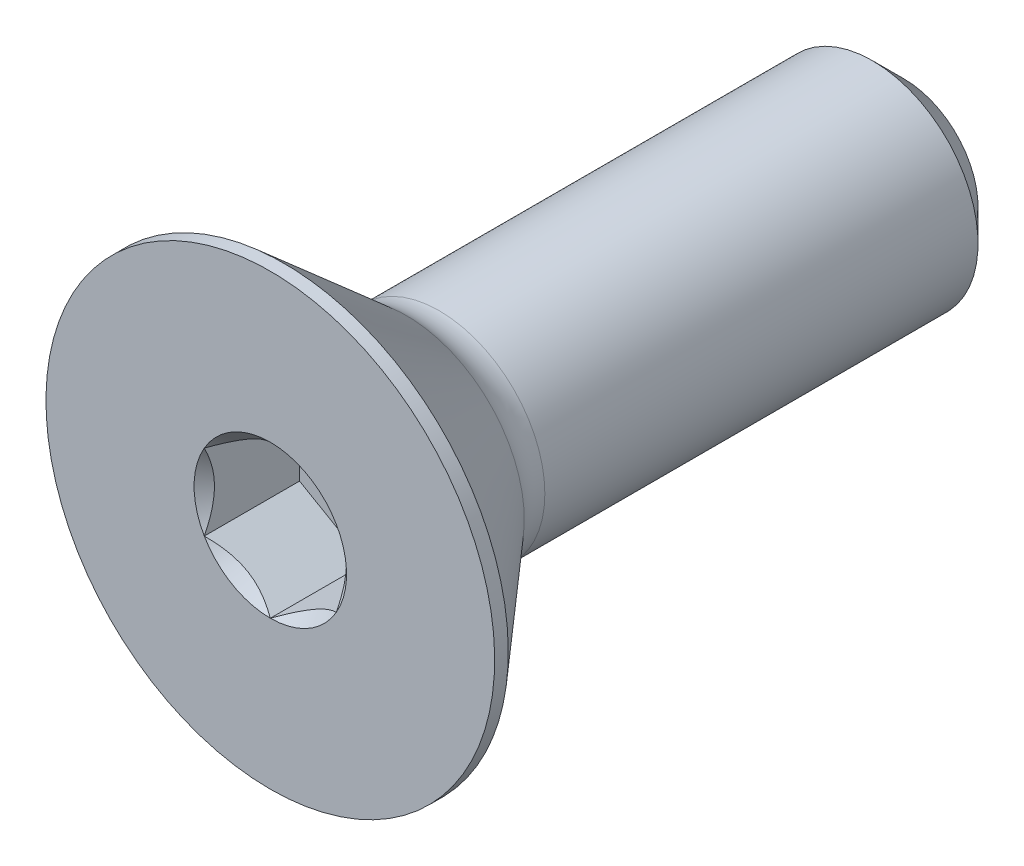
SolidWorks part; units mm, degrees
ref_plane "Front" through (0, 0, 0) normal (0, 0, 1) x (1, 0, 0)
ref_plane "Top" through (0, 0, 0) normal (0, 1, 0) x (1, 0, 0)
ref_plane "Right" through (0, 0, 0) normal (1, 0, 0) x (0, 0, -1)
sketch "Sketch1" plane through (0, 0, 0) normal (1, 0, 0) x (0, 0, -1)
  line L0 (0, 6.7437) -> (0.4089, 6.7437) construction
  line L1 (0.4089, 6.7437) -> (4.0894, 3.5443) construction
  line L2 (0, 3.175) -> (19.05, 3.175)
  line L3 (19.05, 3.175) -> (19.05, 0)
  line L4 (19.05, 0) -> (0, 0)
  line L5 (0, 0) -> (0, 6.7437) construction
  line L6 (0, 6.7437) -> (0, -6.7437) construction
  line L7 (19.05, 3.175) -> (19.05, -3.175) construction
  line L8 (0, -6.7437) -> (0.4089, -6.7437) construction
  line L9 (0.4089, -6.7437) -> (4.0894, -3.5443) construction
  line L11 (0, 3.175) -> (0, 0)
  line L12 (5.0772, 3.175) -> (5.0772, 0) construction
  arc A1 (4.0894, 3.5443) -> (5.0772, 3.175) centre (5.0772, 4.6807) ccw construction
  dimension "D1" = 0.4089
revolve "Revolve1" add sketch "Sketch1" angle 360 mid plane about L4
sketch "Sketch3" plane through (0, 0, -19.05) normal (0, 0, -1) x (-1, 0, 0)
  circle A0 centre (0, 0) radius 3.175
curve "Helix/Spiral1" pitch 1.27 height 19.05 turns 15
sketch "Sketch2" plane through (0, 0, 0) normal (1, 0, 0) x (0, 0, -1)
  line L0 (19.05, 3.175) -> (20.1612, 3.175)
  line L1 (20.1612, 3.175) -> (19.685, 2.3501)
  line L2 (19.685, 2.3501) -> (19.5262, 2.3501)
  line L3 (19.5262, 2.3501) -> (19.05, 3.175)
  line L4 (19.2881, 2.7626) -> (19.9231, 2.7626) construction
  dimension "D1" = 60
  dimension "D2" = 0.1588
  dimension "D3" = 0.635
chamfer "Chamfer1" distance 0.9525 angle 45 1 edges at (0, 3.175, -19.05)
sweep "Cut-Sweep1" [suppressed] cut profiles "Sketch2" path "Helix/Spiral1"
sketch "Sketch7" plane through (0, 0, 0) normal (1, 0, 0) x (0, 0, -1)
  line L0 (0, 6.7437) -> (0.4089, 6.7437) construction
  line L1 (0.4089, 6.7437) -> (4.0894, 3.5443) construction
  line L2 (0, 6.7437) -> (0.4089, 6.7437)
  line L3 (0.4089, 6.7437) -> (4.0894, 3.5443)
  line L4 (5.0772, 3.175) -> (5.0772, 0) construction
  line L5 (5.0772, 3.175) -> (5.0772, 0)
  line L7 (0, 0) -> (0, 6.7437) construction
  line L8 (0, 0) -> (0, 6.7437)
  line L9 (0, 0) -> (5.0772, 0)
  line L10 (7.4181, 0) -> (-7.4181, 0) construction
  arc A0 (4.0894, 3.5443) -> (5.0772, 3.175) centre (5.0772, 4.6807) ccw construction
  arc A1 (4.0894, 3.5443) -> (5.0772, 3.175) centre (5.0772, 4.6807) ccw
revolve "Revolve2" add sketch "Sketch7" angle 360 mid plane about L9
ref_plane "Plane1" through (0, 0, -5.0772) normal (0, 0, 1) x (1, 0, 0)
sketch "Sketch8" plane through (0, 0, -5.0772) normal (0, 0, 1) x (1, 0, 0)
  circle A0 centre (0, 0) radius 3.175
extrude "Boss-Extrude1" add sketch "Sketch8" against normal through all draft 45
sketch "Sketch11" [suppressed] plane through (0, 0, 0) normal (1, 0, 0) x (0, 0, -1)
  line L0 (4.4996, 0) -> (-4.4996, 0) construction
  line L1 (7.3025, 3.8989) -> (1.7272, 3.8989)
  line L2 (7.3025, 3.8989) -> (7.3025, -3.8989)
  line L3 (7.3025, -3.8989) -> (1.7272, -3.8989)
  line L4 (1.7272, 3.8989) -> (1.7272, -3.8989)
  line L5 (0, 3.8989) -> (0.1727, 3.8989) construction
  line L7 (4.7625, 1.7526) -> (4.7625, 0) construction
  point P4 (1.7272, 0)
  dimension "D1" = 2.54
extrude "Cut-Extrude4" [suppressed] cut sketch "Sketch11" against normal through all and the other way through all
combine bodies "Combine1" operation type add bodies to combine 117 108
sketch "Sketch5" plane through (0, 0, 0) normal (0, 0, 1) x (1, 0, 0)
  line L1 (1.9844, -1.1457) -> (1.9844, 1.1457)
  line L2 (1.9844, 1.1457) -> (0, 2.2914)
  line L3 (0, 2.2914) -> (-1.9844, 1.1457)
  line L4 (-1.9844, 1.1457) -> (-1.9844, -1.1457)
  line L5 (-1.9844, -1.1457) -> (0, -2.2914)
  line L6 (0, -2.2914) -> (1.9844, -1.1457)
  circle A0 centre (0, 0) radius 1.9844 construction
  dimension "Hex" = 3.9688
extrude "Cut-Extrude2" cut sketch "Sketch5" against normal blind 2.8626
sketch "Sketch6" plane through (0, 0, 0) normal (0, 0, 1) x (1, 0, 0)
  circle A0 centre (0, 0) radius 2.2914
extrude "Cut-Extrude3" cut sketch "Sketch6" against normal blind 2.8626 draft 45
sketch "Sketch9" [suppressed] plane through (0, 0, -5.0772) normal (0, 0, 1) x (1, 0, 0)
  circle A1 centre (0, 0) radius 3.175
  circle A2 centre (0, 0) radius 3.175
  point P0 (0, 3.175)
  dimension "D1" = 0
extrude "Boss-Extrude2" [suppressed] add sketch "Sketch9" against normal offset from surface (20.3228 mm away) 22.225
sketch "Sketch10" plane through (0, 0, 0) normal (1, 0, 0) x (0, 0, -1)
  line L0 (19.05, 3.175) -> (19.05, -3.175) construction
  point P0 (17.145, -3.175)
  dimension "D1" = 1.905
equation "\"D3@Helix/Spiral1\" = \"Lg@Sketch1\""
equation "\"D2@Sketch2\" = \"D4@Helix/Spiral1\" * .125"
equation "\"D3@Sketch2\" = \"D4@Helix/Spiral1\" * .5"
equation "\"D1@Chamfer1\" = \"D4@Helix/Spiral1\" * .75"
equation "\"D1@Cut-Extrude2\" = \"Head Ht@Sketch1\" * .7"
equation "\"D1@Sketch1\" = \"Head Ht@Sketch1\" * .1"
equation "\"D1@Sketch10\" = \"D4@Helix/Spiral1\" * 1.5"
equation "\"D1@Cut-Extrude3\" = \"D1@Cut-Extrude2\""
